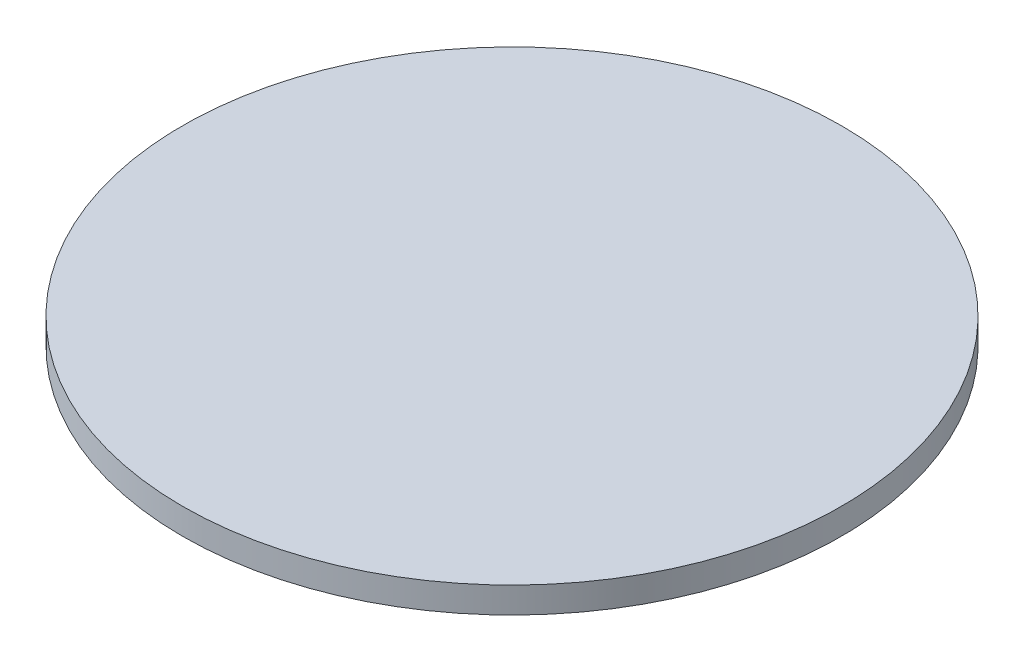
SolidWorks part; units mm, degrees
ref_plane "Front Plane" through (0, 0, 0) normal (0, 0, 1) x (1, 0, 0)
ref_plane "Top Plane" through (0, 0, 0) normal (0, 1, 0) x (1, 0, 0)
ref_plane "Right Plane" through (0, 0, 0) normal (1, 0, 0) x (0, 0, -1)
sketch "Sketch1" plane through (0, 0, 0) normal (0, 1, 0) x (1, 0, 0)
  circle A0 centre (0, 0) radius 25.4508
  dimension "D1" = 50.9016
extrude "Boss-Extrude1" add sketch "Sketch1" along normal blind 2.0066
ref_axis "central axis" through (0, 6.337, 0) along (0, -1, 0)
